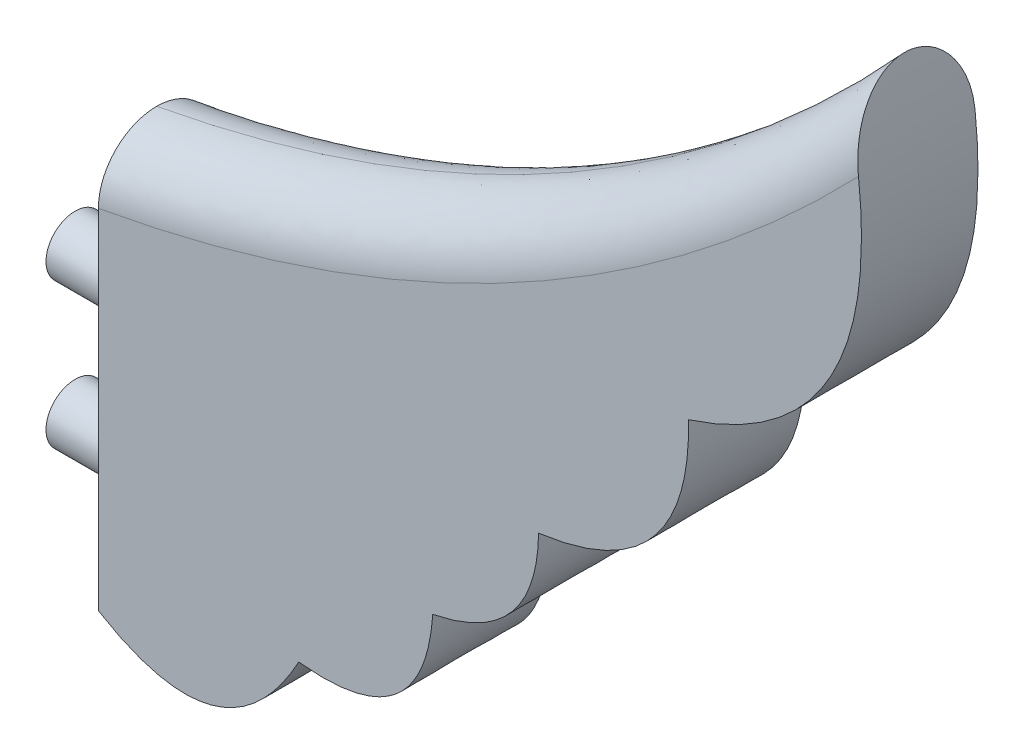
SolidWorks part; units mm, degrees
ref_plane "前基準面" through (0, 0, 0) normal (0, 0, 1) x (1, 0, 0)
ref_plane "上基準面" through (0, 0, 0) normal (0, 1, 0) x (1, 0, 0)
ref_plane "右基準面" through (0, 0, 0) normal (1, 0, 0) x (0, 0, -1)
sketch "草圖1" plane through (0, 0, 0) normal (0, 0, 1) x (1, 0, 0)
  line L0 (-32.7287, 18.8479) -> (-32.7287, -16.1521)
  spline S0 degree 2 poles (-32.7287, 18.8479) (5.0944, 25.874) (31.4472, 54.9368) knots 0 0 0 1 1 1
  spline S1 degree 2 poles (31.4472, 54.9368) (37.192, 29.5822) (17.9178, 23.376) knots 0 0 0 1 1 1
  spline S2 degree 2 poles (17.9178, 23.376) (18.1971, 10.2546) (5.0511, 8.5078) knots 0 0 0 1 1 1
  spline S3 degree 2 poles (5.0511, 8.5078) (4.9229, -0.2729) (-4.0306, -2.0715) knots 0 0 0 1 1 1
  spline S4 degree 2 poles (-32.7287, -16.1521) (-21.783, -22.8262) (-15.5357, -11.3642) knots 0 0 0 1 1 1
  spline S5 degree 2 poles (-15.5357, -11.3642) (-4.7731, -12.5571) (-4.0306, -2.0715) knots 0 0 0 1 1 1
  dimension "D1" = 35
  dimension "D2" = 75
extrude "填料-伸長1" add sketch "草圖1" along normal blind 5 and the other way blind 5
fillet "圓角3" radius 5 3 edges at (31.4472, 54.9368, 0)
sketch "草圖2" plane through (-32.7287, 0, 0) normal (-1, 0, 0) x (0, 0, 1)
  line L0 (-5, -1.1949) -> (5, -1.1949) construction
  line L1 (-5, 13.7623) -> (-5, -16.1521) construction
  line L2 (5, 13.7623) -> (5, -16.1521) construction
  line L3 (0, 18.8479) -> (0, -16.1521) construction
  line L4 (-5, -16.1521) -> (5, -16.1521) construction
  circle A0 centre (0, 5.0551) radius 2.5
  circle A1 centre (0, -7.4449) radius 2.5
  point P15 (0, 0)
  dimension "D1" = 12.5
  dimension "D2" = 6.25
extrude "填料-伸長2" add sketch "草圖2" along normal blind 7
